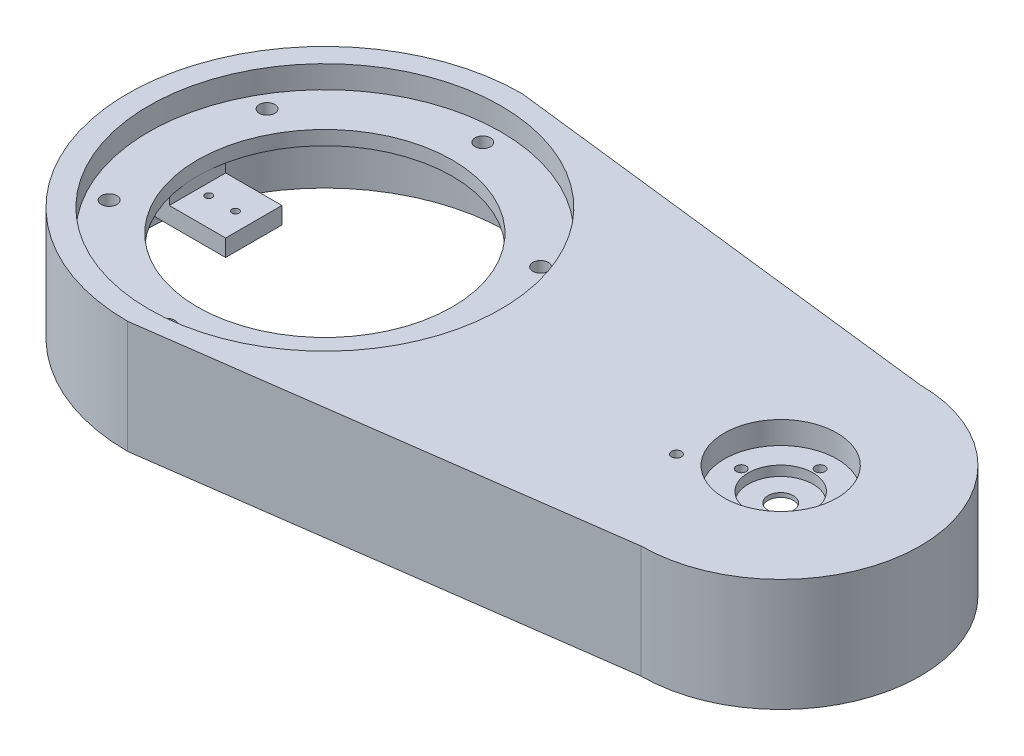
SolidWorks part; units mm, degrees
ref_plane "Front Plane" through (0, 0, 0) normal (0, 0, 1) x (1, 0, 0)
ref_plane "Top Plane" through (0, 0, 0) normal (0, 1, 0) x (1, 0, 0)
ref_plane "Right Plane" through (0, 0, 0) normal (1, 0, 0) x (0, 0, -1)
sketch "Sketch1" plane through (0, 0, 0) normal (0, 1, 0) x (1, 0, 0)
  line L0 (0, 70) -> (160.2226, 51.1021)
  line L1 (160.2226, -47.9524) -> (0, -70)
  arc A0 (0, -70) -> (0, 70) centre (0, 0) cw
  arc A1 (160.2226, -47.9524) -> (160.2226, 51.1021) centre (160.2226, 1.5748) ccw
  circle A3 centre (160.2226, 1.5748) radius 4.25
  circle A4 centre (0, 0) radius 45.22
  circle A5 centre (-56.06, 0) radius 2.75
  circle A7 centre (-28.03, 48.5494) radius 2.75
  circle A8 centre (28.03, 48.5494) radius 2.75
  circle A9 centre (56.06, 0) radius 2.75
  circle A10 centre (28.03, -48.5494) radius 2.75
  circle A11 centre (-28.03, -48.5494) radius 2.75
  dimension "D2" = 56.06
  dimension "D1" = 160.2226
extrude "Boss-Extrude1" add sketch "Sketch1" along normal blind 40 contours L1 A0 L0 A1
sketch "Sketch2" plane through (0, 40, 0) normal (0, 1, 0) x (1, 0, 0)
  circle A0 centre (0, 0) radius 45.22
  circle A2 centre (0, 56.06) radius 2.75
  circle A4 centre (-48.5494, 28.03) radius 2.75
  circle A5 centre (-48.5494, -28.03) radius 2.75
  circle A6 centre (0, -56.06) radius 2.75
  circle A7 centre (48.5494, -28.03) radius 2.75
  circle A8 centre (48.5494, 28.03) radius 2.75
  dimension "D1" = 56.06
extrude "Cut-Extrude1" cut sketch "Sketch2" against normal blind 28
sketch "Sketch4" plane through (0, 40, 0) normal (0, 1, 0) x (1, 0, 0)
  circle A0 centre (0, 0) radius 62.5
extrude "Cut-Extrude2" cut sketch "Sketch4" against normal blind 8
sketch "Sketch5" plane through (0, 0, 0) normal (0, -1, 0) x (1, 0, 0)
  line L3 (160.2226, 42.9552) -> (0, 65)
  line L4 (160.2226, -46.1048) -> (0, -65)
  arc A3 (0, 65) -> (0, -65) centre (0, 0) ccw
  arc A4 (160.2226, 42.9552) -> (160.2226, -46.1048) centre (160.2226, -1.5748) cw
extrude "Cut-Extrude3" cut sketch "Sketch5" against normal blind 27
sketch "Sketch6" plane through (0, 40, 0) normal (0, 1, 0) x (1, 0, 0)
  arc A0 (160.2226, 51.1021) -> (160.2226, -47.9524) centre (160.2226, 1.5748) cw
  arc A1 (160.2226, -47.9524) -> (160.2226, 51.1021) centre (160.2226, 1.5748) ccw construction
  circle A2 centre (160.2226, 1.5748) radius 14
  circle A3 centre (146.2226, 1.5748) radius 1.75
  circle A4 centre (160.2226, 15.5748) radius 1.75
  circle A5 centre (160.2226, -12.4252) radius 1.75
  circle A6 centre (174.2226, 1.5748) radius 1.75
  circle A7 centre (160.2226, 1.5748) radius 4.5
  circle A8 centre (160.2226, 1.5748) radius 11.5
  circle A9 centre (160.2226, 1.5748) radius 20
  dimension "D1" = 0
extrude "Cut-Extrude4" cut sketch "Sketch6" against normal blind 23 contours A7 | A5 | A6 | A4 | A3 region at (160.2226, 40, -1.5748)
extrude "Cut-Extrude5" cut sketch "Sketch6<3>" against normal blind 11.5 contours A8 A7 region at (149.0479, 40, -1.5748)
sketch "Sketch6<3>" plane through (0, 40, 0) normal (0, 1, 0) x (1, 0, 0) same geometry as "Sketch6"
sketch "Sketch7" plane through (0, 27, 0) normal (0, -1, 0) x (1, 0, 0)
  line L5 (-45.22, 0) -> (-45.22, 10)
  line L6 (-45.22, 10) -> (-50.22, 10)
  line L7 (-50.22, 10) -> (-50.22, -10)
  line L8 (-50.22, -10) -> (-45.22, -10)
  line L9 (-45.22, -10) -> (-45.22, 0)
  circle A1 centre (0, 0) radius 45.22 construction
extrude "Boss-Extrude2" add sketch "Sketch7" along normal blind 10
sketch "Sketch8" plane through (-45.22, 0, 0) normal (1, 0, 0) x (0, 0, -1)
  line L0 (10, 17) -> (10, 27) construction
  line L1 (-10, 17) -> (10, 17)
  line L2 (-10, 17) -> (-10, 23)
  line L3 (-10, 23) -> (10, 23)
  line L4 (10, 17) -> (10, 23)
  dimension "D1" = 6
extrude "Boss-Extrude3" add sketch "Sketch8" along normal blind 20
sketch "Sketch9" plane through (0, 17, 0) normal (0, -1, 0) x (1, 0, 0)
  line L0 (-50.22, 10) -> (-50.22, -10) construction
  circle A0 centre (-31.72, 0) radius 1.25
  circle A1 centre (-41.22, 0) radius 1.25
  dimension "D1" = 9.5
  dimension "D2" = 9
extrude "Cut-Extrude6" cut sketch "Sketch9" against normal blind 20
fillet "Fillet1" [suppressed] radius 2.5
extrude "Cut-Extrude7" cut sketch "Sketch6<4>" against normal blind 8 contours A9 A6 A2 A5 A3 A4 | A6 A2 A4 A3 A5 A8 | A8 A7 region at (172.0797, 40, -1.5748) region at (149.0479, 40, -1.5748) region at (140.7883, 40, -1.5748)
sketch "Sketch6<4>" plane through (0, 40, 0) normal (0, 1, 0) x (1, 0, 0) same geometry as "Sketch6"
sketch "Sketch11" plane through (0, 27, 0) normal (0, -1, 0) x (1, 0, 0)
  circle A0 centre (160.2226, -1.5748) radius 4.5
  circle A1 centre (138.2226, 13.4252) radius 1.75
  dimension "D1" = 22
  dimension "D2" = 15
extrude "Cut-Extrude8" cut sketch "Sketch11" against normal blind 168
